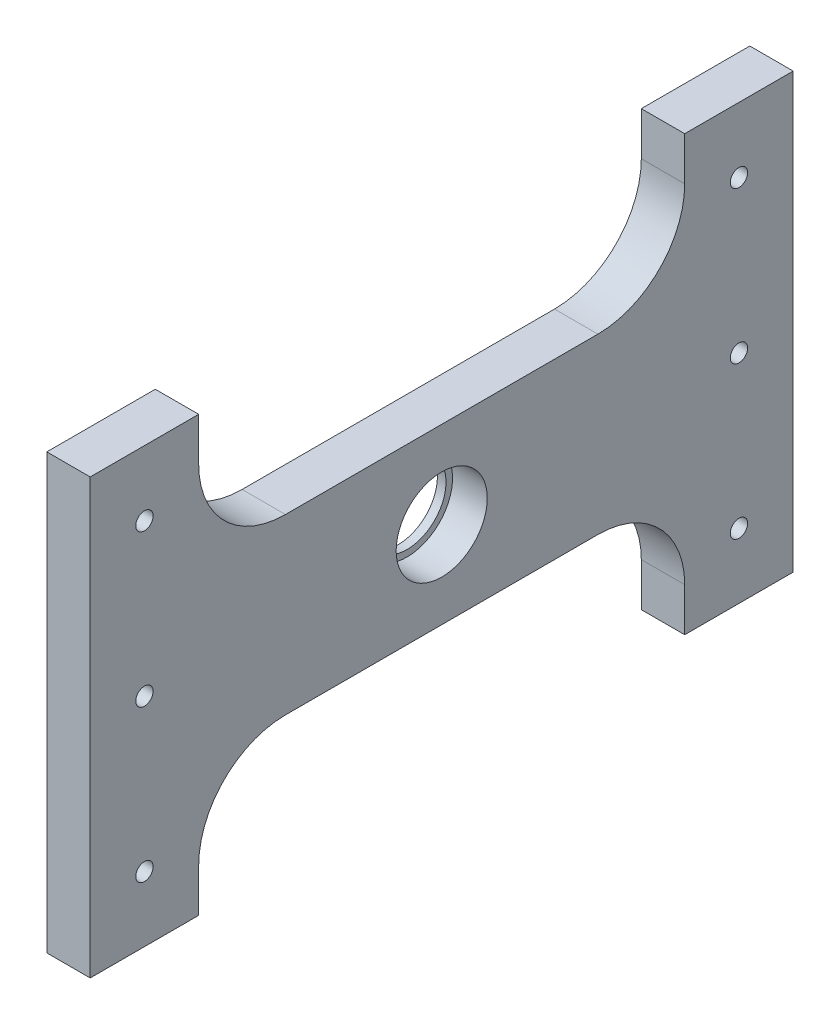
SolidWorks part; units mm, degrees
material "ABS"
ref_plane "Front Plane" through (0, 0, 0) normal (0, 0, 1) x (1, 0, 0)
ref_plane "Top Plane" through (0, 0, 0) normal (0, 1, 0) x (1, 0, 0)
ref_plane "Right Plane" through (0, 0, 0) normal (1, 0, 0) x (0, 0, -1)
sketch "Sketch1" plane through (0, 0, 0) normal (1, 0, 0) x (0, 0, -1)
  line L0 (0, 0) -> (0, -20) construction
  line L1 (-56, -20) -> (56, -20)
  line L2 (-56, -20) -> (-56, 20)
  line L3 (-56, 20) -> (56, 20)
  line L4 (56, -20) -> (56, 20)
  line L5 (-56, -20) -> (56, 20) construction
  line L6 (-56, 20) -> (56, -20) construction
  line L7 (56, -50) -> (81, -50)
  line L8 (56, -50) -> (56, 50)
  line L9 (56, 50) -> (81, 50)
  line L10 (81, -50) -> (81, 50)
  line L11 (56, -50) -> (81, 50) construction
  line L12 (56, 50) -> (81, -50) construction
  line L13 (56, 0) -> (77, 0) construction
  line L14 (-56, 50) -> (-81, 50)
  line L15 (-81, -50) -> (-81, 50)
  line L16 (-56, -50) -> (-81, -50)
  line L17 (-56, -50) -> (-56, 50)
  circle A0 centre (68.5, 35) radius 2
  circle A1 centre (68.5, 0) radius 2
  circle A3 centre (68.5, -35) radius 2
  circle A4 centre (-68.5, -35) radius 2
  circle A5 centre (-68.5, 0) radius 2
  circle A6 centre (-68.5, 35) radius 2
  circle A7 centre (0, 0) radius 10.5
  point P0 (0, 0)
  point P5 (68.5, 0)
  dimension "D7" = 4
  dimension "D8" = 4
  dimension "D9" = 15
  dimension "D10" = 21
  dimension "D11" = 12.5
  dimension "D1" = 112
  dimension "D2" = 40
  dimension "D3" = 25
  dimension "D4" = 100
  dimension "D5" = 12.5
  dimension "D6" = 20
extrude "Boss-Extrude1" add sketch "Sketch1" along normal blind 10 contours L7 L10 L9 L8 L3 L4 L1 A0 A1 A3 | L8 L1 L4 L3 | L17 L1 L8 L3 A7 | L16 L17 L1 L2 L3 L14 L15 A5 A4 A6 | L1 L17 L3 L2 region at (0, 0, 54.8107) region at (0, -35, 57.0308) region at (0, 0, -57.0308)
fillet "Fillet1" radius 20 4 edges at (5, -20, -56) (5, 20, -56) (5, 20, 56) (5, -20, 56)
sketch "Sketch2" plane through (0, 0, 0) normal (-1, 0, 0) x (0, 0, 1)
  circle A0 centre (0, 0) radius 10.5
  circle A1 centre (0, 0) radius 9
  dimension "D1" = 21
  dimension "D2" = 18
extrude "Boss-Extrude2" add sketch "Sketch2" against normal blind 2
